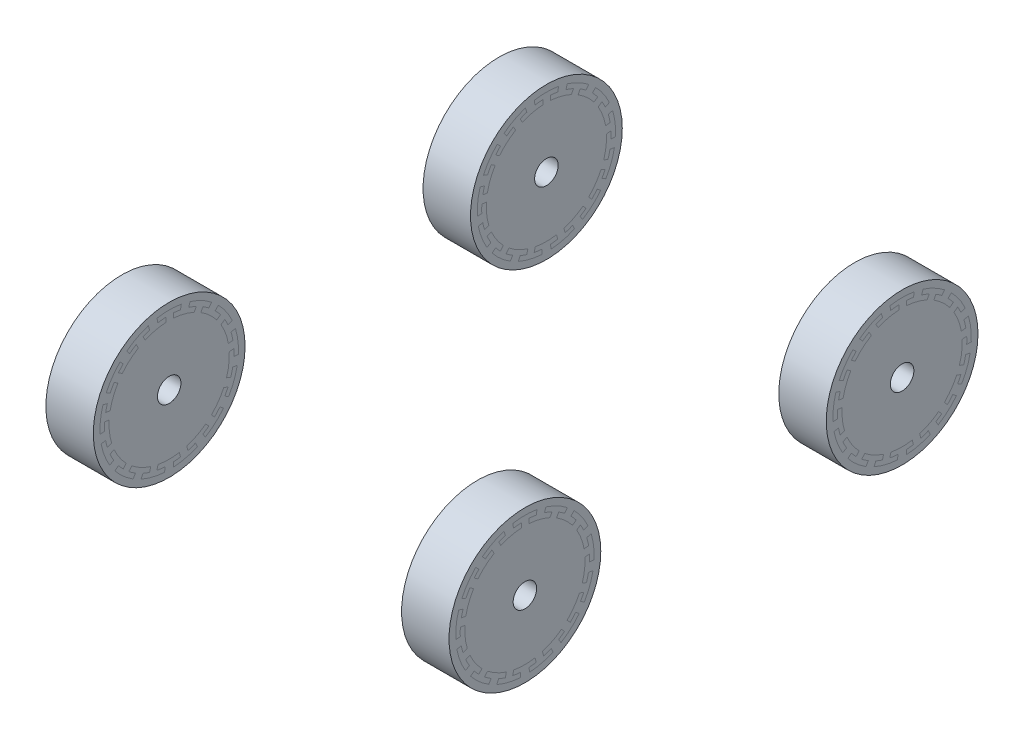
SolidWorks part; units mm, degrees
material "TPU"
ref_plane "Front Plane" through (0, 0, 0) normal (0, 0, 1) x (1, 0, 0)
ref_plane "Top Plane" through (0, 0, 0) normal (0, 1, 0) x (1, 0, 0)
ref_plane "Right Plane" through (0, 0, 0) normal (1, 0, 0) x (0, 0, -1)
ref_plane "Plane1" through (51.59, 0, 0) normal (1, 0, 0) x (0, 0, -1)
sketch "Sketch1" plane through (51.59, 0, 0) normal (1, 0, 0) x (0, 0, -1)
  circle A0 centre (0, 0) radius 25.4 construction
  circle A1 centre (0, 0) radius 3.937
  circle A2 centre (0, 0) radius 5.5562 construction
  circle A3 centre (0, 0) radius 20.1295
  circle A4 centre (0, 0) radius 18.542 construction
  dimension "D1" = 50.8
  dimension "D2" = 1.5875
  dimension "D3" = 6.858
  dimension "D4" = 7.874
  dimension "D5" = 11.1125
extrude "Boss-Extrude1" add sketch "Sketch1" along normal blind 15.875 contours A3 A4 | A2 A1 region at (51.59, 0, 19.5602)
sketch "Sketch3" plane through (51.59, 0, 0) normal (1, 0, 0) x (0, 0, -1)
  line L2 (-4.064, 22.8184) -> (-3.7968, 21.318)
  line L4 (-1.1011, 21.6255) -> (-1.1011, 20.0994)
  line L6 (4.064, 22.8184) -> (3.7968, 21.318)
  line L7 (1.4389, 21.6056) -> (1.4389, 20.078)
  circle A0 centre (0, 0) radius 20.1295 construction
  circle A1 centre (0, 0) radius 20.1295
  arc A2 (-4.064, 22.8184) -> (4.064, 22.8184) centre (0, 0) cw
  arc A3 (-3.7968, 21.318) -> (-1.1011, 21.6255) centre (0, 0) cw
  arc A4 (1.4389, 21.6056) -> (3.7968, 21.318) centre (0, 0) cw
  dimension "D5" = 2.5401
  dimension "D4" = 3.048
  dimension "D1" = 2.54
  dimension "D2" = 1.524
  dimension "D3" = 8.128
extrude "Boss-Extrude3" add sketch "Sketch3" along normal up to surface (15.875 mm away) contours A1 L7 L6 A2 L2 A3 L4 region at (51.59, 21.9601, -0.0412) up to face at (67.465, 0, -3.937)
pattern_circular "CirPattern2" count 13 over 360 about axis through (67.465, 0, 0) along (1, 0, 0) of "Boss-Extrude3"
sketch "Sketch11" plane through (0, 0, 0) normal (0, -0.1753, 0.9845) x (1, 0, 0)
  line L0 (58.5115, 20.8915) -> (60.5435, 20.8915) construction
  line L1 (58.5115, 21.6535) -> (60.5435, 21.6535)
  line L2 (58.5115, 20.1295) -> (60.5435, 20.1295)
  line L3 (67.465, 19.5738) -> (67.465, 20.1295) construction
  line L4 (67.465, 19.5738) -> (67.465, 20.1295) construction
  line L5 (67.465, 21.6535) -> (51.59, 21.6535) construction
  line L6 (67.465, 0) -> (132.0799, 0) construction
  line L7 (67.465, -3.937) -> (67.465, 3.937) construction
  line L8 (67.465, -3.937) -> (67.465, 3.937) construction
  arc A0 (58.5115, 21.6535) -> (58.5115, 20.1295) centre (58.5115, 20.8915) ccw
  arc A1 (60.5435, 20.1295) -> (60.5435, 21.6535) centre (60.5435, 20.8915) ccw
  point P2 (59.5275, 20.8915)
  point P14 (59.5275, 21.6535)
  dimension "D1" = 2.032
revolve "Cut-Revolve1" cut sketch "Sketch11" angle 360 about L6
sketch "Sketch5" plane through (51.59, 0, 0) normal (1, 0, 0) x (0, 0, -1)
  line L4 (-1.1011, 21.6255) -> (-1.1011, 20.0994)
  line L5 (-1.1011, 21.6255) -> (-1.1011, 20.0994)
  line L6 (-4.064, 22.8184) -> (-3.7968, 21.318)
  line L10 (-4.064, 22.8184) -> (-3.7968, 21.318)
  line L35 (3.7968, 21.318) -> (4.064, 22.8184)
  line L38 (3.7968, 21.318) -> (4.064, 22.8184)
  line L42 (1.4389, 20.078) -> (1.4389, 21.6056)
  line L46 (1.4389, 20.078) -> (1.4389, 21.6056)
  line L50 (18.1734, -14.3849) -> (16.9784, -13.439)
  line L54 (18.1734, -14.3849) -> (16.9784, -13.439)
  line L58 (11.2945, -18.4745) -> (12.0895, -19.7748)
  line L62 (11.2945, -18.4745) -> (12.0895, -19.7748)
  line L66 (12.2371, -15.9828) -> (13.2501, -17.1262)
  line L70 (12.2371, -15.9828) -> (13.2501, -17.1262)
  line L110 (9.4067, -21.1828) -> (8.7882, -19.7899)
  line L114 (9.4067, -21.1828) -> (8.7882, -19.7899)
  line L118 (1.4153, -21.6072) -> (1.5149, -23.1279)
  line L120 (15.1645, -15.4568) -> (14.1525, -14.3144)
  line L122 (15.1645, -15.4568) -> (14.1525, -14.3144)
  line L128 (1.4153, -21.6072) -> (1.5149, -23.1279)
  line L136 (6.2444, -20.7336) -> (5.8792, -19.2518)
  line L138 (6.2444, -20.7336) -> (5.8792, -19.2518)
  line L140 (3.4079, -19.8389) -> (3.7735, -21.3222)
  line L148 (-4.1062, -21.2606) -> (-3.741, -19.7788)
  line L149 (-4.1062, -21.2606) -> (-3.741, -19.7788)
  line L156 (-13.5162, -16.9171) -> (-12.5042, -15.7747)
  line L157 (-13.5162, -16.9171) -> (-12.5042, -15.7747)
  line L168 (-19.8297, -8.698) -> (-18.4028, -8.1569)
  line L170 (-19.8297, -8.698) -> (-18.4028, -8.1569)
  line L184 (-21.6005, 1.5136) -> (-20.0855, 1.3297)
  line L186 (-21.6005, 1.5136) -> (-20.0855, 1.3297)
  line L196 (-18.4229, 11.3785) -> (-17.1669, 10.5116)
  line L197 (-18.4229, 11.3785) -> (-17.1669, 10.5116)
  line L204 (-11.0248, 18.6367) -> (-10.3156, 17.2854)
  line L205 (-11.0248, 18.6367) -> (-10.3156, 17.2854)
  line L226 (3.4079, -19.8389) -> (3.7735, -21.3222)
  line L228 (-1.5149, -23.1279) -> (-1.4153, -21.6072)
  line L230 (-1.5149, -23.1279) -> (-1.4153, -21.6072)
  line L232 (-8.7882, -19.7899) -> (-9.4067, -21.1828)
  line L234 (-8.7882, -19.7899) -> (-9.4067, -21.1828)
  line L236 (-6.2021, -19.1502) -> (-6.5677, -20.6335)
  line L238 (-6.2021, -19.1502) -> (-6.5677, -20.6335)
  line L240 (-12.0895, -19.7748) -> (-11.2945, -18.4745)
  line L242 (-12.0895, -19.7748) -> (-11.2945, -18.4745)
  line L244 (-16.9784, -13.439) -> (-18.1734, -14.3849)
  line L245 (-16.9784, -13.439) -> (-18.1734, -14.3849)
  line L246 (-14.3912, -14.0744) -> (-15.4042, -15.2179)
  line L247 (-14.3912, -14.0744) -> (-15.4042, -15.2179)
  line L248 (-19.8945, -11.8914) -> (-18.5864, -11.1095)
  line L249 (-19.8945, -11.8914) -> (-18.5864, -11.1095)
  line L250 (-21.2791, -4.0094) -> (-22.7767, -4.2916)
  line L251 (-21.2791, -4.0094) -> (-22.7767, -4.2916)
  line L252 (-19.2835, -5.7743) -> (-20.7119, -6.3161)
  line L253 (-19.2835, -5.7743) -> (-20.7119, -6.3161)
  line L254 (-23.1419, -1.2839) -> (-21.6203, -1.1995)
  line L255 (-23.1419, -1.2839) -> (-21.6203, -1.1995)
  line L256 (-20.7049, 6.3387) -> (-22.1622, 6.7848)
  line L257 (-20.7049, 6.3387) -> (-22.1622, 6.7848)
  line L258 (-19.7582, 3.8486) -> (-21.2747, 4.0327)
  line L259 (-19.7582, 3.8486) -> (-21.2747, 4.0327)
  line L260 (-21.0878, 9.6177) -> (-19.7012, 8.9853)
  line L261 (-21.0878, 9.6177) -> (-19.7012, 8.9853)
  line L262 (-15.3876, 15.2347) -> (-16.4706, 16.3069)
  line L263 (-15.3876, 15.2347) -> (-16.4706, 16.3069)
  line L264 (-15.7065, 12.5898) -> (-16.9637, 13.4576)
  line L265 (-15.7065, 12.5898) -> (-16.9637, 13.4576)
  line L266 (-14.2027, 18.3161) -> (-13.2689, 17.1117)
  line L267 (-14.2027, 18.3161) -> (-13.2689, 17.1117)
  line L268 (-6.5451, 20.6406) -> (-7.0058, 22.0933)
  line L269 (-6.5451, 20.6406) -> (-7.0058, 22.0933)
  line L270 (-8.0566, 18.4469) -> (-8.7665, 19.7995)
  line L271 (-8.0566, 18.4469) -> (-8.7665, 19.7995)
  line L272 (9.0749, 19.6601) -> (8.3657, 18.3088)
  line L273 (9.0749, 19.6601) -> (8.3657, 18.3088)
  line L274 (7.0058, 22.0933) -> (6.5451, 20.6406)
  line L275 (7.0058, 22.0933) -> (6.5451, 20.6406)
  line L276 (13.2689, 17.1117) -> (14.2027, 18.3161)
  line L277 (13.2689, 17.1117) -> (14.2027, 18.3161)
  line L278 (10.6048, 17.1095) -> (11.3147, 18.4621)
  line L279 (10.6048, 17.1095) -> (11.3147, 18.4621)
  line L280 (17.1719, 13.1909) -> (15.916, 12.3239)
  line L281 (17.1719, 13.1909) -> (15.916, 12.3239)
  line L282 (16.4706, 16.3069) -> (15.3876, 15.2347)
  line L283 (16.4706, 16.3069) -> (15.3876, 15.2347)
  line L284 (19.7012, 8.9853) -> (21.0878, 9.6177)
  line L285 (19.7012, 8.9853) -> (21.0878, 9.6177)
  line L286 (17.3413, 10.2214) -> (18.5985, 11.0892)
  line L287 (17.3413, 10.2214) -> (18.5985, 11.0892)
  line L288 (21.3351, 3.6997) -> (19.8201, 3.5158)
  line L289 (21.3351, 3.6997) -> (19.8201, 3.5158)
  line L290 (22.1622, 6.7848) -> (20.7049, 6.3387)
  line L291 (22.1622, 6.7848) -> (20.7049, 6.3387)
  line L292 (21.6203, -1.1995) -> (23.1419, -1.2839)
  line L293 (21.6203, -1.1995) -> (23.1419, -1.2839)
  line L294 (20.1051, 0.9917) -> (21.6216, 1.1758)
  line L295 (20.1051, 0.9917) -> (21.6216, 1.1758)
  line L296 (20.6106, -6.639) -> (19.1837, -6.0978)
  line L297 (20.6106, -6.639) -> (19.1837, -6.0978)
  line L298 (22.7767, -4.2916) -> (21.2791, -4.0094)
  line L299 (22.7767, -4.2916) -> (21.2791, -4.0094)
  line L300 (18.5864, -11.1095) -> (19.8945, -11.8914)
  line L301 (18.5864, -11.1095) -> (19.8945, -11.8914)
  line L302 (18.263, -8.4652) -> (19.6914, -9.0069)
  line L303 (18.263, -8.4652) -> (19.6914, -9.0069)
  circle A0 centre (0, 0) radius 25.4
  arc A6 (-1.1011, 21.6255) -> (-3.7968, 21.318) centre (0, 0) ccw
  arc A10 (-1.1011, 21.6255) -> (-3.7968, 21.318) centre (0, 0) ccw
  arc A34 (4.064, 22.8184) -> (-4.064, 22.8184) centre (0, 0) ccw
  arc A36 (4.064, 22.8184) -> (-4.064, 22.8184) centre (0, 0) ccw
  arc A37 (-1.1011, 20.0994) -> (-8.0566, 18.4469) centre (0, 0) ccw
  arc A40 (3.7968, 21.318) -> (1.4389, 21.6056) centre (0, 0) ccw
  arc A44 (3.7968, 21.318) -> (1.4389, 21.6056) centre (0, 0) ccw
  arc A48 (15.1645, -15.4568) -> (16.9784, -13.439) centre (0, 0) ccw
  arc A52 (15.1645, -15.4568) -> (16.9784, -13.439) centre (0, 0) ccw
  arc A56 (12.0895, -19.7748) -> (18.1734, -14.3849) centre (0, 0) ccw
  arc A60 (12.0895, -19.7748) -> (18.1734, -14.3849) centre (0, 0) ccw
  arc A64 (11.2945, -18.4745) -> (13.2501, -17.1262) centre (0, 0) ccw
  arc A68 (11.2945, -18.4745) -> (13.2501, -17.1262) centre (0, 0) ccw
  arc A72 (6.2444, -20.7336) -> (8.7882, -19.7899) centre (0, 0) ccw
  arc A73 (-1.1011, 20.0994) -> (-8.0566, 18.4469) centre (0, 0) ccw
  arc A120 (8.3657, 18.3088) -> (1.4389, 20.078) centre (0, 0) ccw
  arc A122 (8.3657, 18.3088) -> (1.4389, 20.078) centre (0, 0) ccw
  arc A136 (5.8792, -19.2518) -> (12.2371, -15.9828) centre (0, 0) ccw
  arc A138 (5.8792, -19.2518) -> (12.2371, -15.9828) centre (0, 0) ccw
  arc A148 (-3.741, -19.7788) -> (3.4079, -19.8389) centre (0, 0) ccw
  arc A149 (-3.741, -19.7788) -> (3.4079, -19.8389) centre (0, 0) ccw
  arc A156 (-12.5042, -15.7747) -> (-6.2021, -19.1502) centre (0, 0) ccw
  arc A157 (-12.5042, -15.7747) -> (-6.2021, -19.1502) centre (0, 0) ccw
  arc A168 (-18.4028, -8.1569) -> (-14.3912, -14.0744) centre (0, 0) ccw
  arc A170 (-18.4028, -8.1569) -> (-14.3912, -14.0744) centre (0, 0) ccw
  arc A184 (-20.0855, 1.3297) -> (-19.2835, -5.7743) centre (0, 0) ccw
  arc A186 (-20.0855, 1.3297) -> (-19.2835, -5.7743) centre (0, 0) ccw
  arc A196 (-17.1669, 10.5116) -> (-19.7582, 3.8486) centre (0, 0) ccw
  arc A197 (-17.1669, 10.5116) -> (-19.7582, 3.8486) centre (0, 0) ccw
  arc A204 (-10.3156, 17.2854) -> (-15.7065, 12.5898) centre (0, 0) ccw
  arc A205 (-10.3156, 17.2854) -> (-15.7065, 12.5898) centre (0, 0) ccw
  arc A208 (6.2444, -20.7336) -> (8.7882, -19.7899) centre (0, 0) ccw
  arc A210 (1.5149, -23.1279) -> (9.4067, -21.1828) centre (0, 0) ccw
  arc A212 (1.5149, -23.1279) -> (9.4067, -21.1828) centre (0, 0) ccw
  arc A214 (1.4153, -21.6072) -> (3.7735, -21.3222) centre (0, 0) ccw
  arc A216 (1.4153, -21.6072) -> (3.7735, -21.3222) centre (0, 0) ccw
  arc A218 (15.916, 12.3239) -> (10.6048, 17.1095) centre (0, 0) ccw
  arc A219 (15.916, 12.3239) -> (10.6048, 17.1095) centre (0, 0) ccw
  arc A220 (-4.1062, -21.2606) -> (-1.4153, -21.6072) centre (0, 0) ccw
  arc A222 (-4.1062, -21.2606) -> (-1.4153, -21.6072) centre (0, 0) ccw
  arc A224 (-9.4067, -21.1828) -> (-1.5149, -23.1279) centre (0, 0) ccw
  arc A226 (19.8201, 3.5158) -> (17.3413, 10.2214) centre (0, 0) ccw
  arc A227 (19.8201, 3.5158) -> (17.3413, 10.2214) centre (0, 0) ccw
  arc A228 (-9.4067, -21.1828) -> (-1.5149, -23.1279) centre (0, 0) ccw
  arc A230 (-8.7882, -19.7899) -> (-6.5677, -20.6335) centre (0, 0) ccw
  arc A232 (-8.7882, -19.7899) -> (-6.5677, -20.6335) centre (0, 0) ccw
  arc A234 (19.1837, -6.0978) -> (20.1051, 0.9917) centre (0, 0) ccw
  arc A235 (19.1837, -6.0978) -> (20.1051, 0.9917) centre (0, 0) ccw
  arc A236 (-13.5162, -16.9171) -> (-11.2945, -18.4745) centre (0, 0) ccw
  arc A238 (-13.5162, -16.9171) -> (-11.2945, -18.4745) centre (0, 0) ccw
  arc A240 (-18.1734, -14.3849) -> (-12.0895, -19.7748) centre (0, 0) ccw
  arc A242 (14.1525, -14.3144) -> (18.263, -8.4652) centre (0, 0) ccw
  arc A243 (14.1525, -14.3144) -> (18.263, -8.4652) centre (0, 0) ccw
  arc A244 (-18.1734, -14.3849) -> (-12.0895, -19.7748) centre (0, 0) ccw
  arc A245 (-16.9784, -13.439) -> (-15.4042, -15.2179) centre (0, 0) ccw
  arc A246 (-16.9784, -13.439) -> (-15.4042, -15.2179) centre (0, 0) ccw
  arc A247 (-19.8297, -8.698) -> (-18.5864, -11.1095) centre (0, 0) ccw
  arc A248 (-19.8297, -8.698) -> (-18.5864, -11.1095) centre (0, 0) ccw
  arc A249 (-22.7767, -4.2916) -> (-19.8945, -11.8914) centre (0, 0) ccw
  arc A250 (-22.7767, -4.2916) -> (-19.8945, -11.8914) centre (0, 0) ccw
  arc A251 (-21.2791, -4.0094) -> (-20.7119, -6.3161) centre (0, 0) ccw
  arc A252 (-21.2791, -4.0094) -> (-20.7119, -6.3161) centre (0, 0) ccw
  arc A253 (-21.6005, 1.5136) -> (-21.6203, -1.1995) centre (0, 0) ccw
  arc A254 (-21.6005, 1.5136) -> (-21.6203, -1.1995) centre (0, 0) ccw
  arc A255 (-22.1622, 6.7848) -> (-23.1419, -1.2839) centre (0, 0) ccw
  arc A256 (-22.1622, 6.7848) -> (-23.1419, -1.2839) centre (0, 0) ccw
  arc A257 (-20.7049, 6.3387) -> (-21.2747, 4.0327) centre (0, 0) ccw
  arc A258 (-20.7049, 6.3387) -> (-21.2747, 4.0327) centre (0, 0) ccw
  arc A259 (-18.4229, 11.3785) -> (-19.7012, 8.9853) centre (0, 0) ccw
  arc A260 (-18.4229, 11.3785) -> (-19.7012, 8.9853) centre (0, 0) ccw
  arc A261 (-16.4706, 16.3069) -> (-21.0878, 9.6177) centre (0, 0) ccw
  arc A262 (-16.4706, 16.3069) -> (-21.0878, 9.6177) centre (0, 0) ccw
  arc A263 (-15.3876, 15.2347) -> (-16.9637, 13.4576) centre (0, 0) ccw
  arc A264 (-15.3876, 15.2347) -> (-16.9637, 13.4576) centre (0, 0) ccw
  arc A265 (-11.0248, 18.6367) -> (-13.2689, 17.1117) centre (0, 0) ccw
  arc A266 (-11.0248, 18.6367) -> (-13.2689, 17.1117) centre (0, 0) ccw
  arc A267 (-7.0058, 22.0933) -> (-14.2027, 18.3161) centre (0, 0) ccw
  arc A268 (-7.0058, 22.0933) -> (-14.2027, 18.3161) centre (0, 0) ccw
  arc A269 (-6.5451, 20.6406) -> (-8.7665, 19.7995) centre (0, 0) ccw
  arc A270 (-6.5451, 20.6406) -> (-8.7665, 19.7995) centre (0, 0) ccw
  arc A271 (9.0749, 19.6601) -> (6.5451, 20.6406) centre (0, 0) ccw
  arc A272 (9.0749, 19.6601) -> (6.5451, 20.6406) centre (0, 0) ccw
  arc A273 (14.2027, 18.3161) -> (7.0058, 22.0933) centre (0, 0) ccw
  arc A274 (14.2027, 18.3161) -> (7.0058, 22.0933) centre (0, 0) ccw
  arc A275 (13.2689, 17.1117) -> (11.3147, 18.4621) centre (0, 0) ccw
  arc A276 (13.2689, 17.1117) -> (11.3147, 18.4621) centre (0, 0) ccw
  arc A277 (17.1719, 13.1909) -> (15.3876, 15.2347) centre (0, 0) ccw
  arc A278 (17.1719, 13.1909) -> (15.3876, 15.2347) centre (0, 0) ccw
  arc A279 (21.0878, 9.6177) -> (16.4706, 16.3069) centre (0, 0) ccw
  arc A280 (21.0878, 9.6177) -> (16.4706, 16.3069) centre (0, 0) ccw
  arc A281 (19.7012, 8.9853) -> (18.5985, 11.0892) centre (0, 0) ccw
  arc A282 (19.7012, 8.9853) -> (18.5985, 11.0892) centre (0, 0) ccw
  arc A283 (21.3351, 3.6997) -> (20.7049, 6.3387) centre (0, 0) ccw
  arc A284 (21.3351, 3.6997) -> (20.7049, 6.3387) centre (0, 0) ccw
  arc A285 (23.1419, -1.2839) -> (22.1622, 6.7848) centre (0, 0) ccw
  arc A286 (23.1419, -1.2839) -> (22.1622, 6.7848) centre (0, 0) ccw
  arc A287 (21.6203, -1.1995) -> (21.6216, 1.1758) centre (0, 0) ccw
  arc A288 (21.6203, -1.1995) -> (21.6216, 1.1758) centre (0, 0) ccw
  arc A289 (20.6106, -6.639) -> (21.2791, -4.0094) centre (0, 0) ccw
  arc A290 (20.6106, -6.639) -> (21.2791, -4.0094) centre (0, 0) ccw
  arc A291 (19.8945, -11.8914) -> (22.7767, -4.2916) centre (0, 0) ccw
  arc A292 (19.8945, -11.8914) -> (22.7767, -4.2916) centre (0, 0) ccw
  arc A293 (18.5864, -11.1095) -> (19.6914, -9.0069) centre (0, 0) ccw
  arc A294 (18.5864, -11.1095) -> (19.6914, -9.0069) centre (0, 0) ccw
  dimension "D1" = 50.8
  dimension "D2" = 0
extrude "Boss-Extrude4" add sketch "Sketch5" along normal up to surface (15.875 mm away) separate body up to face at (67.465, 0, -3.937)
sketch "Sketch4" plane through (0, 0, 0) normal (1, 0, 0) x (0, 0, -1)
  line L0 (0, 0) -> (-126.25, 0) construction
pattern_linear "LPattern1" count 2 spacing 126.25 along (0, 0, 1) of bodies 111 122 107
sketch "Sketch6" plane through (51.59, 0, 0) normal (-1, 0, 0) x (0, 0, 1)
  line L26 (130.0468, 21.318) -> (130.314, 22.8184)
  line L28 (130.0468, 21.318) -> (130.314, 22.8184)
  line L30 (122.186, 22.8184) -> (122.4532, 21.318)
  line L32 (122.186, 22.8184) -> (122.4532, 21.318)
  line L34 (124.8111, 21.6056) -> (124.8111, 20.078)
  line L36 (127.3511, 20.0994) -> (127.3511, 21.6255)
  line L37 (124.8111, 21.6056) -> (124.8111, 20.078)
  line L39 (109.2716, -13.439) -> (108.0766, -14.3849)
  line L40 (112.0975, -14.3144) -> (111.0855, -15.4568)
  line L42 (109.2716, -13.439) -> (108.0766, -14.3849)
  line L44 (120.3708, -19.2518) -> (120.0056, -20.7336)
  line L45 (114.1605, -19.7748) -> (114.9555, -18.4745)
  line L47 (114.1605, -19.7748) -> (114.9555, -18.4745)
  line L48 (129.991, -19.7788) -> (130.3562, -21.2606)
  line L50 (112.9999, -17.1262) -> (114.0129, -15.9828)
  line L52 (138.7542, -15.7747) -> (139.7662, -16.9171)
  line L53 (112.9999, -17.1262) -> (114.0129, -15.9828)
  line L55 (117.4618, -19.7899) -> (116.8433, -21.1828)
  line L56 (144.6528, -8.1569) -> (146.0797, -8.698)
  line L58 (117.4618, -19.7899) -> (116.8433, -21.1828)
  line L60 (146.3355, 1.3297) -> (147.8505, 1.5136)
  line L61 (124.7351, -23.1279) -> (124.8347, -21.6072)
  line L63 (124.7351, -23.1279) -> (124.8347, -21.6072)
  line L64 (143.4169, 10.5116) -> (144.6729, 11.3785)
  line L66 (122.4765, -21.3222) -> (122.8421, -19.8389)
  line L68 (136.5656, 17.2854) -> (137.2748, 18.6367)
  line L72 (127.3511, 20.0994) -> (127.3511, 21.6255)
  line L76 (112.0975, -14.3144) -> (111.0855, -15.4568)
  line L80 (120.3708, -19.2518) -> (120.0056, -20.7336)
  line L84 (129.991, -19.7788) -> (130.3562, -21.2606)
  line L88 (138.7542, -15.7747) -> (139.7662, -16.9171)
  line L92 (144.6528, -8.1569) -> (146.0797, -8.698)
  line L96 (146.3355, 1.3297) -> (147.8505, 1.5136)
  line L100 (143.4169, 10.5116) -> (144.6729, 11.3785)
  line L104 (136.5656, 17.2854) -> (137.2748, 18.6367)
  line L138 (122.4765, -21.3222) -> (122.8421, -19.8389)
  line L140 (127.6653, -21.6072) -> (127.7649, -23.1279)
  line L142 (127.6653, -21.6072) -> (127.7649, -23.1279)
  line L144 (135.6567, -21.1828) -> (135.0382, -19.7899)
  line L146 (135.6567, -21.1828) -> (135.0382, -19.7899)
  line L148 (132.8177, -20.6335) -> (132.4521, -19.1502)
  line L150 (132.8177, -20.6335) -> (132.4521, -19.1502)
  line L152 (137.5445, -18.4745) -> (138.3395, -19.7748)
  line L154 (137.5445, -18.4745) -> (138.3395, -19.7748)
  line L156 (144.4234, -14.3849) -> (143.2284, -13.439)
  line L157 (144.4234, -14.3849) -> (143.2284, -13.439)
  line L158 (141.6542, -15.2179) -> (140.6412, -14.0744)
  line L159 (141.6542, -15.2179) -> (140.6412, -14.0744)
  line L160 (144.8363, -11.1095) -> (146.1445, -11.8914)
  line L161 (144.8363, -11.1095) -> (146.1445, -11.8914)
  line L162 (149.0267, -4.2916) -> (147.5291, -4.0094)
  line L163 (149.0267, -4.2916) -> (147.5291, -4.0094)
  line L164 (146.9619, -6.3161) -> (145.5335, -5.7743)
  line L165 (146.9619, -6.3161) -> (145.5335, -5.7743)
  line L166 (147.8703, -1.1995) -> (149.3919, -1.2839)
  line L167 (147.8703, -1.1995) -> (149.3919, -1.2839)
  line L168 (148.4122, 6.7848) -> (146.9549, 6.3387)
  line L169 (148.4122, 6.7848) -> (146.9549, 6.3387)
  line L170 (147.5247, 4.0327) -> (146.0082, 3.8486)
  line L171 (147.5247, 4.0327) -> (146.0082, 3.8486)
  line L172 (145.9512, 8.9853) -> (147.3378, 9.6177)
  line L173 (145.9512, 8.9853) -> (147.3378, 9.6177)
  line L174 (142.7206, 16.3069) -> (141.6376, 15.2347)
  line L175 (142.7206, 16.3069) -> (141.6376, 15.2347)
  line L176 (143.2137, 13.4576) -> (141.9565, 12.5898)
  line L177 (143.2137, 13.4576) -> (141.9565, 12.5898)
  line L178 (139.5189, 17.1117) -> (140.4527, 18.3161)
  line L179 (139.5189, 17.1117) -> (140.4527, 18.3161)
  line L180 (133.2558, 22.0933) -> (132.7951, 20.6406)
  line L181 (133.2558, 22.0933) -> (132.7951, 20.6406)
  line L182 (135.0165, 19.7995) -> (134.3066, 18.4469)
  line L183 (135.0165, 19.7995) -> (134.3066, 18.4469)
  line L184 (117.8843, 18.3088) -> (117.1751, 19.6601)
  line L185 (117.8843, 18.3088) -> (117.1751, 19.6601)
  line L186 (119.7049, 20.6406) -> (119.2442, 22.0933)
  line L187 (119.7049, 20.6406) -> (119.2442, 22.0933)
  line L188 (112.0473, 18.3161) -> (112.9811, 17.1117)
  line L189 (112.0473, 18.3161) -> (112.9811, 17.1117)
  line L190 (114.9353, 18.4621) -> (115.6452, 17.1095)
  line L191 (114.9353, 18.4621) -> (115.6452, 17.1095)
  line L192 (110.334, 12.3239) -> (109.0781, 13.1909)
  line L193 (110.334, 12.3239) -> (109.0781, 13.1909)
  line L194 (110.8624, 15.2347) -> (109.7794, 16.3069)
  line L195 (110.8624, 15.2347) -> (109.7794, 16.3069)
  line L196 (105.1622, 9.6177) -> (106.5488, 8.9853)
  line L197 (105.1622, 9.6177) -> (106.5488, 8.9853)
  line L198 (107.6515, 11.0892) -> (108.9087, 10.2214)
  line L199 (107.6515, 11.0892) -> (108.9087, 10.2214)
  line L200 (106.4299, 3.5158) -> (104.9149, 3.6997)
  line L201 (106.4299, 3.5158) -> (104.9149, 3.6997)
  line L202 (105.545, 6.3387) -> (104.0878, 6.7848)
  line L203 (105.545, 6.3387) -> (104.0878, 6.7848)
  line L204 (103.1081, -1.2839) -> (104.6297, -1.1995)
  line L205 (103.1081, -1.2839) -> (104.6297, -1.1995)
  line L206 (104.6284, 1.1758) -> (106.1449, 0.9917)
  line L207 (104.6284, 1.1758) -> (106.1449, 0.9917)
  line L208 (107.0663, -6.0978) -> (105.6394, -6.639)
  line L209 (107.0663, -6.0978) -> (105.6394, -6.639)
  line L210 (104.9709, -4.0094) -> (103.4733, -4.2916)
  line L211 (104.9709, -4.0094) -> (103.4733, -4.2916)
  line L212 (106.3555, -11.8914) -> (107.6636, -11.1095)
  line L213 (106.3555, -11.8914) -> (107.6636, -11.1095)
  line L214 (106.5586, -9.0069) -> (107.987, -8.4652)
  line L215 (106.5586, -9.0069) -> (107.987, -8.4652)
  circle A0 centre (126.25, 0) radius 3.937 construction
  circle A1 centre (126.25, 0) radius 3.937
  arc A28 (130.0468, 21.318) -> (127.3511, 21.6255) centre (126.25, 0) ccw
  arc A30 (130.0468, 21.318) -> (127.3511, 21.6255) centre (126.25, 0) ccw
  arc A32 (130.314, 22.8184) -> (122.186, 22.8184) centre (126.25, 0) ccw
  arc A34 (130.314, 22.8184) -> (122.186, 22.8184) centre (126.25, 0) ccw
  arc A36 (134.3066, 18.4469) -> (127.3511, 20.0994) centre (126.25, 0) ccw
  arc A37 (124.8111, 21.6056) -> (122.4532, 21.318) centre (126.25, 0) ccw
  arc A39 (124.8111, 21.6056) -> (122.4532, 21.318) centre (126.25, 0) ccw
  arc A40 (124.8111, 20.078) -> (117.8843, 18.3088) centre (126.25, 0) ccw
  arc A42 (109.2716, -13.439) -> (111.0855, -15.4568) centre (126.25, 0) ccw
  arc A44 (114.0129, -15.9828) -> (120.3708, -19.2518) centre (126.25, 0) ccw
  arc A45 (109.2716, -13.439) -> (111.0855, -15.4568) centre (126.25, 0) ccw
  arc A47 (108.0766, -14.3849) -> (114.1605, -19.7748) centre (126.25, 0) ccw
  arc A48 (122.8421, -19.8389) -> (129.991, -19.7788) centre (126.25, 0) ccw
  arc A50 (108.0766, -14.3849) -> (114.1605, -19.7748) centre (126.25, 0) ccw
  arc A52 (132.4521, -19.1502) -> (138.7542, -15.7747) centre (126.25, 0) ccw
  arc A53 (112.9999, -17.1262) -> (114.9555, -18.4745) centre (126.25, 0) ccw
  arc A55 (112.9999, -17.1262) -> (114.9555, -18.4745) centre (126.25, 0) ccw
  arc A56 (140.6412, -14.0744) -> (144.6528, -8.1569) centre (126.25, 0) ccw
  arc A58 (117.4618, -19.7899) -> (120.0056, -20.7336) centre (126.25, 0) ccw
  arc A60 (145.5335, -5.7743) -> (146.3355, 1.3297) centre (126.25, 0) ccw
  arc A64 (146.0082, 3.8486) -> (143.4169, 10.5116) centre (126.25, 0) ccw
  arc A68 (141.9565, 12.5898) -> (136.5656, 17.2854) centre (126.25, 0) ccw
  arc A72 (134.3066, 18.4469) -> (127.3511, 20.0994) centre (126.25, 0) ccw
  arc A76 (124.8111, 20.078) -> (117.8843, 18.3088) centre (126.25, 0) ccw
  arc A80 (114.0129, -15.9828) -> (120.3708, -19.2518) centre (126.25, 0) ccw
  arc A84 (122.8421, -19.8389) -> (129.991, -19.7788) centre (126.25, 0) ccw
  arc A88 (132.4521, -19.1502) -> (138.7542, -15.7747) centre (126.25, 0) ccw
  arc A92 (140.6412, -14.0744) -> (144.6528, -8.1569) centre (126.25, 0) ccw
  arc A96 (145.5335, -5.7743) -> (146.3355, 1.3297) centre (126.25, 0) ccw
  arc A100 (146.0082, 3.8486) -> (143.4169, 10.5116) centre (126.25, 0) ccw
  arc A104 (141.9565, 12.5898) -> (136.5656, 17.2854) centre (126.25, 0) ccw
  arc A126 (117.4618, -19.7899) -> (120.0056, -20.7336) centre (126.25, 0) ccw
  arc A128 (116.8433, -21.1828) -> (124.7351, -23.1279) centre (126.25, 0) ccw
  arc A130 (115.6452, 17.1095) -> (110.334, 12.3239) centre (126.25, 0) ccw
  arc A131 (115.6452, 17.1095) -> (110.334, 12.3239) centre (126.25, 0) ccw
  arc A132 (116.8433, -21.1828) -> (124.7351, -23.1279) centre (126.25, 0) ccw
  arc A134 (122.4765, -21.3222) -> (124.8347, -21.6072) centre (126.25, 0) ccw
  arc A136 (122.4765, -21.3222) -> (124.8347, -21.6072) centre (126.25, 0) ccw
  arc A138 (108.9087, 10.2214) -> (106.4299, 3.5158) centre (126.25, 0) ccw
  arc A139 (108.9087, 10.2214) -> (106.4299, 3.5158) centre (126.25, 0) ccw
  arc A140 (127.6653, -21.6072) -> (130.3562, -21.2606) centre (126.25, 0) ccw
  arc A142 (127.6653, -21.6072) -> (130.3562, -21.2606) centre (126.25, 0) ccw
  arc A144 (127.7649, -23.1279) -> (135.6567, -21.1828) centre (126.25, 0) ccw
  arc A146 (106.1449, 0.9917) -> (107.0663, -6.0978) centre (126.25, 0) ccw
  arc A147 (106.1449, 0.9917) -> (107.0663, -6.0978) centre (126.25, 0) ccw
  arc A148 (127.7649, -23.1279) -> (135.6567, -21.1828) centre (126.25, 0) ccw
  arc A150 (132.8177, -20.6335) -> (135.0382, -19.7899) centre (126.25, 0) ccw
  arc A152 (132.8177, -20.6335) -> (135.0382, -19.7899) centre (126.25, 0) ccw
  arc A154 (107.987, -8.4652) -> (112.0975, -14.3144) centre (126.25, 0) ccw
  arc A155 (107.987, -8.4652) -> (112.0975, -14.3144) centre (126.25, 0) ccw
  arc A156 (137.5445, -18.4745) -> (139.7662, -16.9171) centre (126.25, 0) ccw
  arc A157 (137.5445, -18.4745) -> (139.7662, -16.9171) centre (126.25, 0) ccw
  arc A158 (138.3395, -19.7748) -> (144.4234, -14.3849) centre (126.25, 0) ccw
  arc A159 (138.3395, -19.7748) -> (144.4234, -14.3849) centre (126.25, 0) ccw
  arc A160 (141.6542, -15.2179) -> (143.2284, -13.439) centre (126.25, 0) ccw
  arc A161 (141.6542, -15.2179) -> (143.2284, -13.439) centre (126.25, 0) ccw
  arc A162 (144.8363, -11.1095) -> (146.0797, -8.698) centre (126.25, 0) ccw
  arc A163 (144.8363, -11.1095) -> (146.0797, -8.698) centre (126.25, 0) ccw
  arc A164 (146.1445, -11.8914) -> (149.0267, -4.2916) centre (126.25, 0) ccw
  arc A165 (146.1445, -11.8914) -> (149.0267, -4.2916) centre (126.25, 0) ccw
  arc A166 (146.9619, -6.3161) -> (147.5291, -4.0094) centre (126.25, 0) ccw
  arc A167 (146.9619, -6.3161) -> (147.5291, -4.0094) centre (126.25, 0) ccw
  arc A168 (147.8703, -1.1995) -> (147.8505, 1.5136) centre (126.25, 0) ccw
  arc A169 (147.8703, -1.1995) -> (147.8505, 1.5136) centre (126.25, 0) ccw
  arc A170 (149.3919, -1.2839) -> (148.4122, 6.7848) centre (126.25, 0) ccw
  arc A171 (149.3919, -1.2839) -> (148.4122, 6.7848) centre (126.25, 0) ccw
  arc A172 (147.5247, 4.0327) -> (146.9549, 6.3387) centre (126.25, 0) ccw
  arc A173 (147.5247, 4.0327) -> (146.9549, 6.3387) centre (126.25, 0) ccw
  arc A174 (145.9512, 8.9853) -> (144.6729, 11.3785) centre (126.25, 0) ccw
  arc A175 (145.9512, 8.9853) -> (144.6729, 11.3785) centre (126.25, 0) ccw
  arc A176 (147.3378, 9.6177) -> (142.7206, 16.3069) centre (126.25, 0) ccw
  arc A177 (147.3378, 9.6177) -> (142.7206, 16.3069) centre (126.25, 0) ccw
  arc A178 (143.2137, 13.4576) -> (141.6376, 15.2347) centre (126.25, 0) ccw
  arc A179 (143.2137, 13.4576) -> (141.6376, 15.2347) centre (126.25, 0) ccw
  arc A180 (139.5189, 17.1117) -> (137.2748, 18.6367) centre (126.25, 0) ccw
  arc A181 (139.5189, 17.1117) -> (137.2748, 18.6367) centre (126.25, 0) ccw
  arc A182 (140.4527, 18.3161) -> (133.2558, 22.0933) centre (126.25, 0) ccw
  arc A183 (140.4527, 18.3161) -> (133.2558, 22.0933) centre (126.25, 0) ccw
  arc A184 (135.0165, 19.7995) -> (132.7951, 20.6406) centre (126.25, 0) ccw
  arc A185 (135.0165, 19.7995) -> (132.7951, 20.6406) centre (126.25, 0) ccw
  arc A186 (119.7049, 20.6406) -> (117.1751, 19.6601) centre (126.25, 0) ccw
  arc A187 (119.7049, 20.6406) -> (117.1751, 19.6601) centre (126.25, 0) ccw
  arc A188 (119.2442, 22.0933) -> (112.0473, 18.3161) centre (126.25, 0) ccw
  arc A189 (119.2442, 22.0933) -> (112.0473, 18.3161) centre (126.25, 0) ccw
  arc A190 (114.9353, 18.4621) -> (112.9811, 17.1117) centre (126.25, 0) ccw
  arc A191 (114.9353, 18.4621) -> (112.9811, 17.1117) centre (126.25, 0) ccw
  arc A192 (110.8624, 15.2347) -> (109.0781, 13.1909) centre (126.25, 0) ccw
  arc A193 (110.8624, 15.2347) -> (109.0781, 13.1909) centre (126.25, 0) ccw
  arc A194 (109.7794, 16.3069) -> (105.1622, 9.6177) centre (126.25, 0) ccw
  arc A195 (109.7794, 16.3069) -> (105.1622, 9.6177) centre (126.25, 0) ccw
  arc A196 (107.6515, 11.0892) -> (106.5488, 8.9853) centre (126.25, 0) ccw
  arc A197 (107.6515, 11.0892) -> (106.5488, 8.9853) centre (126.25, 0) ccw
  arc A198 (105.545, 6.3387) -> (104.9149, 3.6997) centre (126.25, 0) ccw
  arc A199 (105.545, 6.3387) -> (104.9149, 3.6997) centre (126.25, 0) ccw
  arc A200 (104.0878, 6.7848) -> (103.1081, -1.2839) centre (126.25, 0) ccw
  arc A201 (104.0878, 6.7848) -> (103.1081, -1.2839) centre (126.25, 0) ccw
  arc A202 (104.6284, 1.1758) -> (104.6297, -1.1995) centre (126.25, 0) ccw
  arc A203 (104.6284, 1.1758) -> (104.6297, -1.1995) centre (126.25, 0) ccw
  arc A204 (104.9709, -4.0094) -> (105.6394, -6.639) centre (126.25, 0) ccw
  arc A205 (104.9709, -4.0094) -> (105.6394, -6.639) centre (126.25, 0) ccw
  arc A206 (103.4733, -4.2916) -> (106.3555, -11.8914) centre (126.25, 0) ccw
  arc A207 (103.4733, -4.2916) -> (106.3555, -11.8914) centre (126.25, 0) ccw
  arc A208 (106.5586, -9.0069) -> (107.6636, -11.1095) centre (126.25, 0) ccw
  arc A209 (106.5586, -9.0069) -> (107.6636, -11.1095) centre (126.25, 0) ccw
  dimension "D1" = 0
extrude "Boss-Extrude6" [suppressed] add sketch "Sketch6" along normal up to surface (5.2 mm away)
sketch "Sketch7" [suppressed] plane through (49.92, 0, 0) normal (-1, 0, 0) x (0, 0, 1)
  line L36 (127.3511, 20.0994) -> (127.3511, 21.6255)
  line L37 (130.0468, 21.318) -> (130.314, 22.8184)
  line L38 (122.186, 22.8184) -> (122.4532, 21.318)
  line L39 (124.8111, 21.6056) -> (124.8111, 20.078)
  line L40 (112.0975, -14.3144) -> (111.0855, -15.4568)
  line L41 (109.2716, -13.439) -> (108.0766, -14.3849)
  line L42 (114.1605, -19.7748) -> (114.9555, -18.4745)
  line L43 (112.9999, -17.1262) -> (114.0129, -15.9828)
  line L44 (120.3708, -19.2518) -> (120.0056, -20.7336)
  line L45 (117.4618, -19.7899) -> (116.8433, -21.1828)
  line L46 (124.7351, -23.1279) -> (124.8347, -21.6072)
  line L47 (122.4765, -21.3222) -> (122.8421, -19.8389)
  line L48 (129.991, -19.7788) -> (130.3562, -21.2606)
  line L49 (127.6653, -21.6072) -> (127.7649, -23.1279)
  line L50 (135.6567, -21.1828) -> (135.0382, -19.7899)
  line L51 (132.8177, -20.6335) -> (132.4521, -19.1502)
  line L52 (138.7542, -15.7747) -> (139.7662, -16.9171)
  line L53 (137.5445, -18.4745) -> (138.3395, -19.7748)
  line L54 (144.4234, -14.3849) -> (143.2284, -13.439)
  line L55 (141.6542, -15.2179) -> (140.6412, -14.0744)
  line L56 (144.6528, -8.1569) -> (146.0797, -8.698)
  line L57 (144.8363, -11.1095) -> (146.1445, -11.8914)
  line L58 (149.0267, -4.2916) -> (147.5291, -4.0094)
  line L59 (146.9619, -6.3161) -> (145.5335, -5.7743)
  line L60 (146.3355, 1.3297) -> (147.8505, 1.5136)
  line L61 (147.8703, -1.1995) -> (149.3919, -1.2839)
  line L62 (148.4122, 6.7848) -> (146.9549, 6.3387)
  line L63 (147.5247, 4.0327) -> (146.0082, 3.8486)
  line L64 (143.4169, 10.5116) -> (144.6729, 11.3785)
  line L65 (145.9512, 8.9853) -> (147.3378, 9.6177)
  line L66 (142.7206, 16.3069) -> (141.6376, 15.2347)
  line L67 (143.2137, 13.4576) -> (141.9565, 12.5898)
  line L68 (136.5656, 17.2854) -> (137.2748, 18.6367)
  line L69 (139.5189, 17.1117) -> (140.4527, 18.3161)
  line L70 (133.2558, 22.0933) -> (132.7951, 20.6406)
  line L71 (135.0165, 19.7995) -> (134.3066, 18.4469)
  line L72 (127.3511, 20.0994) -> (127.3511, 21.6255)
  line L73 (130.0468, 21.318) -> (130.314, 22.8184)
  line L74 (122.186, 22.8184) -> (122.4532, 21.318)
  line L75 (124.8111, 21.6056) -> (124.8111, 20.078)
  line L76 (112.0975, -14.3144) -> (111.0855, -15.4568)
  line L77 (109.2716, -13.439) -> (108.0766, -14.3849)
  line L78 (114.1605, -19.7748) -> (114.9555, -18.4745)
  line L79 (112.9999, -17.1262) -> (114.0129, -15.9828)
  line L80 (120.3708, -19.2518) -> (120.0056, -20.7336)
  line L81 (117.4618, -19.7899) -> (116.8433, -21.1828)
  line L82 (124.7351, -23.1279) -> (124.8347, -21.6072)
  line L83 (122.4765, -21.3222) -> (122.8421, -19.8389)
  line L84 (129.991, -19.7788) -> (130.3562, -21.2606)
  line L85 (127.6653, -21.6072) -> (127.7649, -23.1279)
  line L86 (135.6567, -21.1828) -> (135.0382, -19.7899)
  line L87 (132.8177, -20.6335) -> (132.4521, -19.1502)
  line L88 (138.7542, -15.7747) -> (139.7662, -16.9171)
  line L89 (137.5445, -18.4745) -> (138.3395, -19.7748)
  line L90 (144.4234, -14.3849) -> (143.2284, -13.439)
  line L91 (141.6542, -15.2179) -> (140.6412, -14.0744)
  line L92 (144.6528, -8.1569) -> (146.0797, -8.698)
  line L93 (144.8363, -11.1095) -> (146.1445, -11.8914)
  line L94 (149.0267, -4.2916) -> (147.5291, -4.0094)
  line L95 (146.9619, -6.3161) -> (145.5335, -5.7743)
  line L96 (146.3355, 1.3297) -> (147.8505, 1.5136)
  line L97 (147.8703, -1.1995) -> (149.3919, -1.2839)
  line L98 (148.4122, 6.7848) -> (146.9549, 6.3387)
  line L99 (147.5247, 4.0327) -> (146.0082, 3.8486)
  line L100 (143.4169, 10.5116) -> (144.6729, 11.3785)
  line L101 (145.9512, 8.9853) -> (147.3378, 9.6177)
  line L102 (142.7206, 16.3069) -> (141.6376, 15.2347)
  line L103 (143.2137, 13.4576) -> (141.9565, 12.5898)
  line L104 (136.5656, 17.2854) -> (137.2748, 18.6367)
  line L105 (139.5189, 17.1117) -> (140.4527, 18.3161)
  line L106 (133.2558, 22.0933) -> (132.7951, 20.6406)
  line L107 (135.0165, 19.7995) -> (134.3066, 18.4469)
  line L124 (117.8843, 18.3088) -> (117.1751, 19.6601)
  line L125 (117.8843, 18.3088) -> (117.1751, 19.6601)
  line L126 (119.7049, 20.6406) -> (119.2442, 22.0933)
  line L127 (119.7049, 20.6406) -> (119.2442, 22.0933)
  line L128 (112.0473, 18.3161) -> (112.9811, 17.1117)
  line L129 (112.0473, 18.3161) -> (112.9811, 17.1117)
  line L130 (114.9353, 18.4621) -> (115.6452, 17.1095)
  line L131 (114.9353, 18.4621) -> (115.6452, 17.1095)
  line L132 (110.334, 12.3239) -> (109.0781, 13.1909)
  line L133 (110.334, 12.3239) -> (109.0781, 13.1909)
  line L134 (110.8624, 15.2347) -> (109.7794, 16.3069)
  line L135 (110.8624, 15.2347) -> (109.7794, 16.3069)
  line L136 (105.1622, 9.6177) -> (106.5488, 8.9853)
  line L137 (105.1622, 9.6177) -> (106.5488, 8.9853)
  line L138 (107.6515, 11.0892) -> (108.9087, 10.2214)
  line L139 (107.6515, 11.0892) -> (108.9087, 10.2214)
  line L140 (106.4299, 3.5158) -> (104.9149, 3.6997)
  line L141 (106.4299, 3.5158) -> (104.9149, 3.6997)
  line L142 (105.545, 6.3387) -> (104.0878, 6.7848)
  line L143 (105.545, 6.3387) -> (104.0878, 6.7848)
  line L144 (103.1081, -1.2839) -> (104.6297, -1.1995)
  line L145 (103.1081, -1.2839) -> (104.6297, -1.1995)
  line L146 (104.6284, 1.1758) -> (106.1449, 0.9917)
  line L147 (104.6284, 1.1758) -> (106.1449, 0.9917)
  line L148 (107.0663, -6.0978) -> (105.6394, -6.639)
  line L149 (107.0663, -6.0978) -> (105.6394, -6.639)
  line L150 (104.9709, -4.0094) -> (103.4733, -4.2916)
  line L151 (104.9709, -4.0094) -> (103.4733, -4.2916)
  line L152 (106.3555, -11.8914) -> (107.6636, -11.1095)
  line L153 (106.3555, -11.8914) -> (107.6636, -11.1095)
  line L154 (106.5586, -9.0069) -> (107.987, -8.4652)
  line L155 (106.5586, -9.0069) -> (107.987, -8.4652)
  circle A1 centre (126.25, 0) radius 25.4
  circle A2 centre (126.25, 0) radius 25.4
  arc A38 (130.0468, 21.318) -> (127.3511, 21.6255) centre (126.25, 0) ccw
  arc A39 (130.314, 22.8184) -> (122.186, 22.8184) centre (126.25, 0) ccw
  arc A40 (124.8111, 21.6056) -> (122.4532, 21.318) centre (126.25, 0) ccw
  arc A41 (124.8111, 20.078) -> (117.8843, 18.3088) centre (126.25, 0) ccw
  arc A42 (109.2716, -13.439) -> (111.0855, -15.4568) centre (126.25, 0) ccw
  arc A43 (108.0766, -14.3849) -> (114.1605, -19.7748) centre (126.25, 0) ccw
  arc A44 (112.9999, -17.1262) -> (114.9555, -18.4745) centre (126.25, 0) ccw
  arc A45 (114.0129, -15.9828) -> (120.3708, -19.2518) centre (126.25, 0) ccw
  arc A46 (117.4618, -19.7899) -> (120.0056, -20.7336) centre (126.25, 0) ccw
  arc A47 (116.8433, -21.1828) -> (124.7351, -23.1279) centre (126.25, 0) ccw
  arc A48 (122.4765, -21.3222) -> (124.8347, -21.6072) centre (126.25, 0) ccw
  arc A49 (122.8421, -19.8389) -> (129.991, -19.7788) centre (126.25, 0) ccw
  arc A50 (127.6653, -21.6072) -> (130.3562, -21.2606) centre (126.25, 0) ccw
  arc A51 (127.7649, -23.1279) -> (135.6567, -21.1828) centre (126.25, 0) ccw
  arc A52 (132.8177, -20.6335) -> (135.0382, -19.7899) centre (126.25, 0) ccw
  arc A53 (132.4521, -19.1502) -> (138.7542, -15.7747) centre (126.25, 0) ccw
  arc A54 (137.5445, -18.4745) -> (139.7662, -16.9171) centre (126.25, 0) ccw
  arc A55 (138.3395, -19.7748) -> (144.4234, -14.3849) centre (126.25, 0) ccw
  arc A56 (141.6542, -15.2179) -> (143.2284, -13.439) centre (126.25, 0) ccw
  arc A57 (140.6412, -14.0744) -> (144.6528, -8.1569) centre (126.25, 0) ccw
  arc A58 (144.8363, -11.1095) -> (146.0797, -8.698) centre (126.25, 0) ccw
  arc A59 (146.1445, -11.8914) -> (149.0267, -4.2916) centre (126.25, 0) ccw
  arc A60 (146.9619, -6.3161) -> (147.5291, -4.0094) centre (126.25, 0) ccw
  arc A61 (145.5335, -5.7743) -> (146.3355, 1.3297) centre (126.25, 0) ccw
  arc A62 (147.8703, -1.1995) -> (147.8505, 1.5136) centre (126.25, 0) ccw
  arc A63 (149.3919, -1.2839) -> (148.4122, 6.7848) centre (126.25, 0) ccw
  arc A64 (147.5247, 4.0327) -> (146.9549, 6.3387) centre (126.25, 0) ccw
  arc A65 (146.0082, 3.8486) -> (143.4169, 10.5116) centre (126.25, 0) ccw
  arc A66 (145.9512, 8.9853) -> (144.6729, 11.3785) centre (126.25, 0) ccw
  arc A67 (147.3378, 9.6177) -> (142.7206, 16.3069) centre (126.25, 0) ccw
  arc A68 (143.2137, 13.4576) -> (141.6376, 15.2347) centre (126.25, 0) ccw
  arc A69 (141.9565, 12.5898) -> (136.5656, 17.2854) centre (126.25, 0) ccw
  arc A70 (139.5189, 17.1117) -> (137.2748, 18.6367) centre (126.25, 0) ccw
  arc A71 (140.4527, 18.3161) -> (133.2558, 22.0933) centre (126.25, 0) ccw
  arc A72 (135.0165, 19.7995) -> (132.7951, 20.6406) centre (126.25, 0) ccw
  arc A73 (134.3066, 18.4469) -> (127.3511, 20.0994) centre (126.25, 0) ccw
  arc A74 (130.0468, 21.318) -> (127.3511, 21.6255) centre (126.25, 0) ccw
  arc A75 (130.314, 22.8184) -> (122.186, 22.8184) centre (126.25, 0) ccw
  arc A76 (124.8111, 21.6056) -> (122.4532, 21.318) centre (126.25, 0) ccw
  arc A77 (124.8111, 20.078) -> (117.8843, 18.3088) centre (126.25, 0) ccw
  arc A78 (109.2716, -13.439) -> (111.0855, -15.4568) centre (126.25, 0) ccw
  arc A79 (108.0766, -14.3849) -> (114.1605, -19.7748) centre (126.25, 0) ccw
  arc A80 (112.9999, -17.1262) -> (114.9555, -18.4745) centre (126.25, 0) ccw
  arc A81 (114.0129, -15.9828) -> (120.3708, -19.2518) centre (126.25, 0) ccw
  arc A82 (117.4618, -19.7899) -> (120.0056, -20.7336) centre (126.25, 0) ccw
  arc A83 (116.8433, -21.1828) -> (124.7351, -23.1279) centre (126.25, 0) ccw
  arc A84 (122.4765, -21.3222) -> (124.8347, -21.6072) centre (126.25, 0) ccw
  arc A85 (122.8421, -19.8389) -> (129.991, -19.7788) centre (126.25, 0) ccw
  arc A86 (127.6653, -21.6072) -> (130.3562, -21.2606) centre (126.25, 0) ccw
  arc A87 (127.7649, -23.1279) -> (135.6567, -21.1828) centre (126.25, 0) ccw
  arc A88 (132.8177, -20.6335) -> (135.0382, -19.7899) centre (126.25, 0) ccw
  arc A89 (132.4521, -19.1502) -> (138.7542, -15.7747) centre (126.25, 0) ccw
  arc A90 (137.5445, -18.4745) -> (139.7662, -16.9171) centre (126.25, 0) ccw
  arc A91 (138.3395, -19.7748) -> (144.4234, -14.3849) centre (126.25, 0) ccw
  arc A92 (141.6542, -15.2179) -> (143.2284, -13.439) centre (126.25, 0) ccw
  arc A93 (140.6412, -14.0744) -> (144.6528, -8.1569) centre (126.25, 0) ccw
  arc A94 (144.8363, -11.1095) -> (146.0797, -8.698) centre (126.25, 0) ccw
  arc A95 (146.1445, -11.8914) -> (149.0267, -4.2916) centre (126.25, 0) ccw
  arc A96 (146.9619, -6.3161) -> (147.5291, -4.0094) centre (126.25, 0) ccw
  arc A97 (145.5335, -5.7743) -> (146.3355, 1.3297) centre (126.25, 0) ccw
  arc A98 (147.8703, -1.1995) -> (147.8505, 1.5136) centre (126.25, 0) ccw
  arc A99 (149.3919, -1.2839) -> (148.4122, 6.7848) centre (126.25, 0) ccw
  arc A100 (147.5247, 4.0327) -> (146.9549, 6.3387) centre (126.25, 0) ccw
  arc A101 (146.0082, 3.8486) -> (143.4169, 10.5116) centre (126.25, 0) ccw
  arc A102 (145.9512, 8.9853) -> (144.6729, 11.3785) centre (126.25, 0) ccw
  arc A103 (147.3378, 9.6177) -> (142.7206, 16.3069) centre (126.25, 0) ccw
  arc A104 (143.2137, 13.4576) -> (141.6376, 15.2347) centre (126.25, 0) ccw
  arc A105 (141.9565, 12.5898) -> (136.5656, 17.2854) centre (126.25, 0) ccw
  arc A106 (139.5189, 17.1117) -> (137.2748, 18.6367) centre (126.25, 0) ccw
  arc A107 (140.4527, 18.3161) -> (133.2558, 22.0933) centre (126.25, 0) ccw
  arc A108 (135.0165, 19.7995) -> (132.7951, 20.6406) centre (126.25, 0) ccw
  arc A109 (134.3066, 18.4469) -> (127.3511, 20.0994) centre (126.25, 0) ccw
  arc A126 (119.7049, 20.6406) -> (117.1751, 19.6601) centre (126.25, 0) ccw
  arc A127 (119.7049, 20.6406) -> (117.1751, 19.6601) centre (126.25, 0) ccw
  arc A128 (119.2442, 22.0933) -> (112.0473, 18.3161) centre (126.25, 0) ccw
  arc A129 (119.2442, 22.0933) -> (112.0473, 18.3161) centre (126.25, 0) ccw
  arc A130 (114.9353, 18.4621) -> (112.9811, 17.1117) centre (126.25, 0) ccw
  arc A131 (114.9353, 18.4621) -> (112.9811, 17.1117) centre (126.25, 0) ccw
  arc A132 (115.6452, 17.1095) -> (110.334, 12.3239) centre (126.25, 0) ccw
  arc A133 (115.6452, 17.1095) -> (110.334, 12.3239) centre (126.25, 0) ccw
  arc A134 (110.8624, 15.2347) -> (109.0781, 13.1909) centre (126.25, 0) ccw
  arc A135 (110.8624, 15.2347) -> (109.0781, 13.1909) centre (126.25, 0) ccw
  arc A136 (109.7794, 16.3069) -> (105.1622, 9.6177) centre (126.25, 0) ccw
  arc A137 (109.7794, 16.3069) -> (105.1622, 9.6177) centre (126.25, 0) ccw
  arc A138 (107.6515, 11.0892) -> (106.5488, 8.9853) centre (126.25, 0) ccw
  arc A139 (107.6515, 11.0892) -> (106.5488, 8.9853) centre (126.25, 0) ccw
  arc A140 (108.9087, 10.2214) -> (106.4299, 3.5158) centre (126.25, 0) ccw
  arc A141 (108.9087, 10.2214) -> (106.4299, 3.5158) centre (126.25, 0) ccw
  arc A142 (105.545, 6.3387) -> (104.9149, 3.6997) centre (126.25, 0) ccw
  arc A143 (105.545, 6.3387) -> (104.9149, 3.6997) centre (126.25, 0) ccw
  arc A144 (104.0878, 6.7848) -> (103.1081, -1.2839) centre (126.25, 0) ccw
  arc A145 (104.0878, 6.7848) -> (103.1081, -1.2839) centre (126.25, 0) ccw
  arc A146 (104.6284, 1.1758) -> (104.6297, -1.1995) centre (126.25, 0) ccw
  arc A147 (104.6284, 1.1758) -> (104.6297, -1.1995) centre (126.25, 0) ccw
  arc A148 (106.1449, 0.9917) -> (107.0663, -6.0978) centre (126.25, 0) ccw
  arc A149 (106.1449, 0.9917) -> (107.0663, -6.0978) centre (126.25, 0) ccw
  arc A150 (104.9709, -4.0094) -> (105.6394, -6.639) centre (126.25, 0) ccw
  arc A151 (104.9709, -4.0094) -> (105.6394, -6.639) centre (126.25, 0) ccw
  arc A152 (103.4733, -4.2916) -> (106.3555, -11.8914) centre (126.25, 0) ccw
  arc A153 (103.4733, -4.2916) -> (106.3555, -11.8914) centre (126.25, 0) ccw
  arc A154 (106.5586, -9.0069) -> (107.6636, -11.1095) centre (126.25, 0) ccw
  arc A155 (106.5586, -9.0069) -> (107.6636, -11.1095) centre (126.25, 0) ccw
  arc A156 (107.987, -8.4652) -> (112.0975, -14.3144) centre (126.25, 0) ccw
  arc A157 (107.987, -8.4652) -> (112.0975, -14.3144) centre (126.25, 0) ccw
  dimension "D1" = 0
  dimension "D2" = 0
extrude "Boss-Extrude7" [suppressed] add sketch "Sketch7" along normal up to surface (5.2 mm away) up to face at (67.465, 0, 122.313)
sketch "Sketch12" [suppressed] plane through (0, -21.794, 122.3684) normal (0, -0.1753, 0.9845) x (1, 0, 0)
  line L0 (50.054, 43.0285) -> (52.086, 43.0285) construction
  line L1 (50.054, 43.7905) -> (52.086, 43.7905)
  line L2 (50.054, 42.2665) -> (52.086, 42.2665)
  line L3 (62.62, 43.7905) -> (44.72, 43.7905) construction
  line L4 (44.72, 42.2665) -> (44.72, 41.7108) construction
  line L5 (44.72, 42.2665) -> (44.72, 41.7108) construction
  line L6 (65.795, 18.2) -> (65.795, 26.074) construction
  line L7 (65.795, 18.2) -> (65.795, 26.074) construction
  line L8 (65.795, 22.137) -> (30.8633, 22.137) construction
  arc A0 (50.054, 43.7905) -> (50.054, 42.2665) centre (50.054, 43.0285) ccw
  arc A1 (52.086, 42.2665) -> (52.086, 43.7905) centre (52.086, 43.0285) ccw
  point P2 (51.07, 43.0285)
  dimension "D1" = 2.032
  dimension "D2" = 6.35
revolve "Cut-Revolve2" [suppressed] cut sketch "Sketch12" angle 360 about L8
sketch "Sketch13" [suppressed] plane through (51.99, 0, 0) normal (-1, 0, 0) x (0, 0, 1)
  circle A0 centre (126.25, 0) radius 14.239 construction
  circle A1 centre (126.25, 0) radius 14.239
  circle A2 centre (126.25, 0) radius 3.937 construction
  circle A3 centre (126.25, 0) radius 3.937
extrude "Boss-Extrude8" [suppressed] add sketch "Sketch13" along normal up to surface (18.8425 mm away)
chamfer "Chamfer1" [suppressed] distance 5.08 angle 45
ref_plane "Plane3" [suppressed] through (0, -21.794, 122.3684) normal (0, -0.1753, 0.9845) x (1, 0, 0)
mirror "Mirror1" about plane through (0, 0, 0) normal (1, 0, 0) of bodies 122 108 112 111 107
